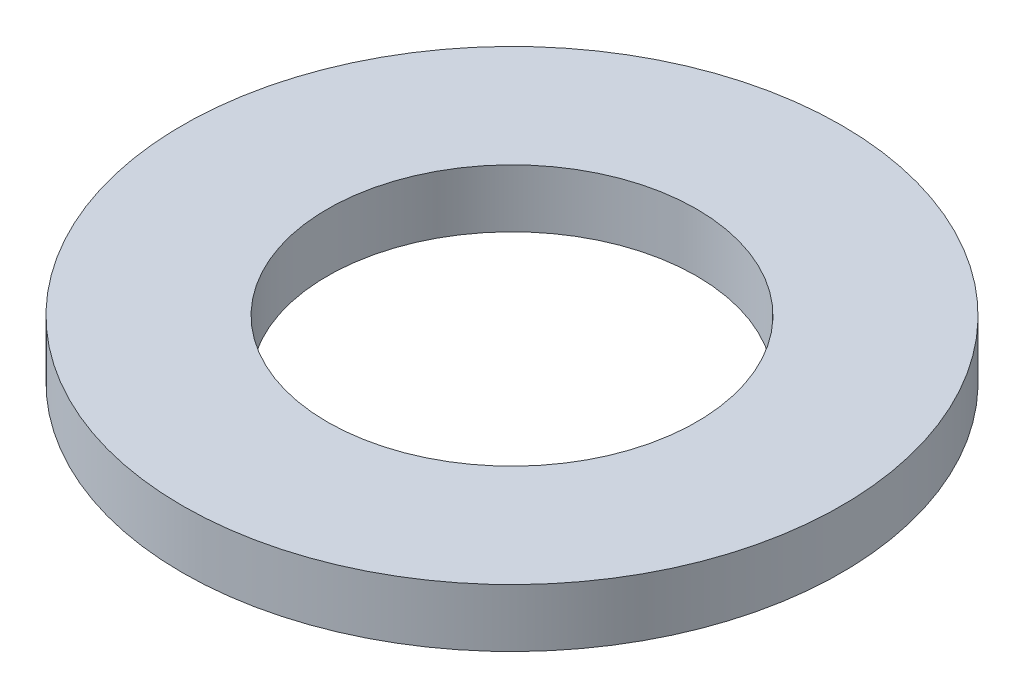
SolidWorks part; units mm, degrees
ref_plane "Front Plane" through (0, 0, 0) normal (0, 0, 1) x (1, 0, 0)
ref_plane "Top Plane" through (0, 0, 0) normal (0, 1, 0) x (1, 0, 0)
ref_plane "Right Plane" through (0, 0, 0) normal (1, 0, 0) x (0, 0, -1)
sketch "Sketch1" plane through (0, 0, 0) normal (0, 1, 0) x (1, 0, 0)
  circle A0 centre (0, 0) radius 62.5
  dimension "FLANGE_OD" = 125
extrude "Boss-Extrude1" add sketch "Sketch1" along normal blind 11
sketch "Sketch2" plane through (0, 0, 0) normal (0, 1, 0) x (1, 0, 0)
  circle A0 centre (0, 0) radius 35
  dimension "BORE_D" = 70
extrude "Cut-Extrude1" cut sketch "Sketch2" along normal through all
sketch "Sketch3" plane through (0, 11, 0) normal (0, 1, 0) x (1, 0, 0)
  circle A0 centre (0, 0) radius 26.5757 construction
  circle A1 centre (-26.5757, 0) radius 2.9767
  dimension "BOLT_D" = 5.9534
  dimension "BOLT_PCD" = 53.1513
extrude "Cut-Extrude2" cut sketch "Sketch3" against normal blind 8.0327 rebuild error yes
pattern_circular "CirPattern1" count 3 over 360 rebuild error yes
